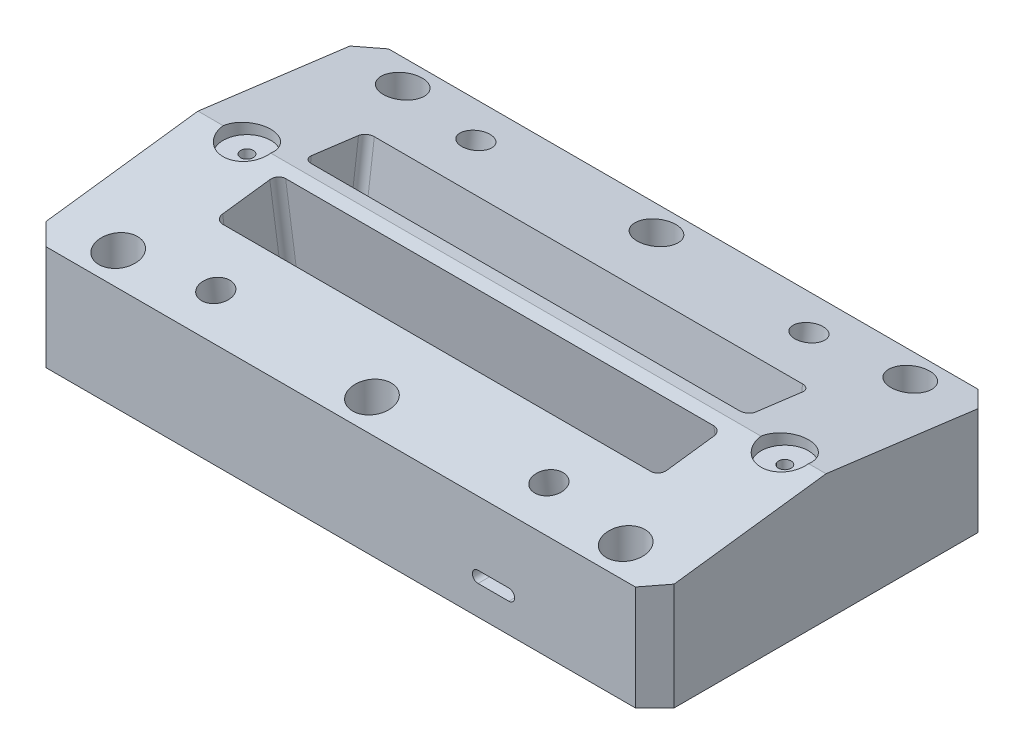
SolidWorks part; units mm, degrees
material "Custom Plastic"
ref_plane "Front Plane" through (0, 0, 0) normal (0, 0, 1) x (1, 0, 0)
ref_plane "Top Plane" through (0, 0, 0) normal (0, 1, 0) x (1, 0, 0)
ref_plane "Right Plane" through (0, 0, 0) normal (1, 0, 0) x (0, 0, -1)
sketch "Sketch1" plane through (0, 0, 0) normal (0, 1, 0) x (1, 0, 0)
  line L1 (0, 0) -> (198, 0)
  line L2 (0, 0) -> (0, 108)
  line L3 (0, 108) -> (198, 108)
  line L4 (198, 0) -> (198, 108)
  dimension "D1" = 198
  dimension "D2" = 108
extrude "Boss-Extrude1" add sketch "Sketch1" along normal blind 40
ref_plane "Left" through (198, 0, 0) normal (1, 0, 0) x (0, 0, -1)
ref_plane "Bot" through (0, 40, 0) normal (0, 1, 0) x (1, 0, 0)
ref_plane "der loco" through (0, 0, -52) normal (0, 0, -1) x (-1, 0, 0)
sketch "Sketch4" plane through (0, 0, 0) normal (0, 1, 0) x (1, 0, 0)
  line L0 (0, 108) -> (0, 0) construction
  line L1 (8.5, 31.5) -> (189.5, 31.5)
  line L2 (8.5, 31.5) -> (8.5, 76.5)
  line L3 (8.5, 76.5) -> (189.5, 76.5)
  line L4 (189.5, 31.5) -> (189.5, 76.5)
  line L5 (0, 0) -> (198, 0) construction
  dimension "D1" = 181
  dimension "D2" = 8.5
  dimension "D3" = 45
  dimension "D4" = 31.5
extrude "Cut-Extrude2" cut sketch "Sketch4" along normal blind 10 contours L2 L1 L4 L3
ref_plane "Plane32" through (0, 10, 0) normal (0, -1, 0) x (-1, 0, 0)
sketch "Sketch5" plane through (198, 0, 0) normal (1, 0, 0) x (0, 0, -1)
  line L0 (54, 40) -> (108, 33.0345)
  line L1 (0, 40) -> (108, 40) construction
  line L2 (108, 33.0345) -> (108, 40)
  line L3 (108, 40) -> (54, 40)
  line L4 (108, 40) -> (108, 0) construction
  dimension "D1" = 7.35
  dimension "D2" = 54
extrude "Cut-Extrude3" cut sketch "Sketch5" against normal up to vertex (198 mm away) up to point (0, 40, 0)
ref_plane "Plane24" through (0, 10, 0) normal (0, -1, 0) x (-1, 0, 0)
sketch "Sketch53" plane through (0, 10, 0) normal (0, -1, 0) x (-1, 0, 0)
  line L0 (-8.5, 51.5) -> (-8.5, 31.5)
  line L1 (-8.5, 76.5) -> (-8.5, 31.5) construction
  line L2 (-8.5, 31.5) -> (-39.5, 31.5)
  line L3 (-8.5, 31.5) -> (-189.5, 31.5) construction
  line L4 (-39.5, 31.5) -> (-8.5, 51.5)
  line L5 (-8.5, 54) -> (-189.5, 54) construction
  line L6 (-189.5, 31.5) -> (-189.5, 76.5) construction
  line L7 (-8.5, 56.5) -> (-8.5, 76.5)
  line L8 (-8.5, 76.5) -> (-39.5, 76.5)
  line L9 (-39.5, 76.5) -> (-8.5, 56.5)
  line L10 (-99, 76.5) -> (-99, 31.5) construction
  line L11 (-8.5, 76.5) -> (-189.5, 76.5) construction
  line L12 (-8.5, 31.5) -> (-189.5, 31.5) construction
  line L13 (-158.5, 76.5) -> (-189.5, 56.5)
  line L14 (-189.5, 76.5) -> (-158.5, 76.5)
  line L15 (-189.5, 56.5) -> (-189.5, 76.5)
  line L16 (-158.5, 31.5) -> (-189.5, 51.5)
  line L17 (-189.5, 31.5) -> (-158.5, 31.5)
  line L18 (-189.5, 51.5) -> (-189.5, 31.5)
  dimension "D1" = 31
  dimension "D2" = 20
extrude "Boss-Extrude11" add sketch "Sketch53" along normal up to surface (10 mm away) up to face at (99, 0, -54)
ref_plane "izq loco" through (0, 0, -57) normal (0, 0, -1) x (-1, 0, 0)
sketch "Sketch18" plane through (198, 0, 0) normal (1, 0, 0) x (0, 0, -1)
  line L0 (0, 33.0345) -> (0, 40)
  line L1 (0, 40) -> (0, 0) construction
  line L2 (0, 40) -> (54, 40)
  line L3 (54, 40) -> (0, 33.0345)
  line L4 (0, 40) -> (54, 40) construction
  dimension "D1" = 54
  dimension "D2" = 7.35
extrude "Cut-Extrude12" cut sketch "Sketch18" against normal up to surface (198 mm away) up to face at (0, 22.6069, -54)
sketch "Sketch60" plane through (0, 0, 0) normal (0, 1, 0) x (1, 0, 0)
  point P0 (8.5, 31.5)
  point P1 (39.5, 31.5)
  point P2 (8.5, 76.5)
  point P6 (39.5, 76.5)
  dimension "D1" = 20
  dimension "D2" = 31
  dimension "D3" = 20
  dimension "D4" = 31
ref_axis "Axis6" through (8.5, 0, -31.5) along (1, 0, 0)
sketch "Sketch69" plane through (0, 10, 0) normal (0, -1, 0) x (-1, 0, 0)
  point P0 (-39.5, 56.5)
  point P1 (-8.5, 51.5)
  point P2 (-38.5, 51.5)
  point P3 (-8.5, 56.5)
  dimension "D1" = 31
  dimension "D2" = 20
  dimension "D3" = 20
  dimension "D4" = 30
sketch "der loco axis" plane through (0, 0, -52) normal (0, 0, -1) x (-1, 0, 0)
  point P0 (-8.5, 8.5)
  point P1 (-38.5, 8.5)
  dimension "D1" = 1.5
sketch "izq loco axis" plane through (0, 0, -57) normal (0, 0, -1) x (-1, 0, 0)
  line L0 (-39.5, 0) -> (-39.5, 10) construction
  line L1 (-8.5, 0) -> (-8.5, 10) construction
  point P0 (-8.5, 8.4959)
  point P1 (-39.5, 8.4959)
  dimension "D1" = 1.5041
ref_plane "Plane3" through (0, 46.1968, -5.9589) normal (0, 0.9918, -0.1279) x (1, 0, 0)
ref_axis "Axis8" through (39.5, 0, -76.5) along (-1, 0, 0)
ref_axis "Axis9" through (8.5, 8.4959, -57) along (1, 0, 0)
ref_axis "Axis10" through (38.5, 8.5, -52) along (-1, 0, 0)
ref_plane "Izq bueno" through (0, 28.0127, -12.2048) normal (0, 0.9168, -0.3994) x (1, 0, 0)
sketch "Izq" plane through (0, 28.0127, -12.2048) normal (0, 0.9168, -0.3994) x (1, 0, 0)
  line L0 (8.5, 48.8622) -> (29.5, 70.1326)
  line L1 (29.5, 70.1326) -> (8.5, 70.1326)
  line L2 (8.5, 70.1326) -> (8.5, 48.8622)
  dimension "D1" = 21
extrude "Cut-Extrude28" cut sketch "Izq" against normal blind 14.5
ref_plane "Der bueno" through (0, -11.1449, -4.6211) normal (0, 0.9237, 0.383) x (1, 0, 0)
sketch "Der" plane through (0, -11.1449, -4.6211) normal (0, 0.9237, 0.383) x (1, 0, 0)
  line L0 (8.5, 51.2902) -> (29.5, 29.0979)
  line L1 (29.5, 29.0979) -> (8.5, 29.0979)
  line L2 (8.5, 29.0979) -> (8.5, 51.2902)
  dimension "D1" = 21
extrude "Cut-Extrude29" cut sketch "Der" against normal blind 14.5
sketch "Sketch97" plane through (0, 0, 0) normal (0, 1, 0) x (1, 0, 0)
  line L0 (8.5, 57.5) -> (29.5, 76.5)
  line L1 (29.5, 76.5) -> (158.5, 76.5)
  line L3 (158.5, 31.5) -> (29.5, 31.5)
  line L4 (29.5, 31.5) -> (8.5, 51.5)
  line L5 (8.5, 51.5) -> (8.5, 57.5)
  line L7 (158.5, 76.5) -> (189.5, 56.5)
  line L8 (189.5, 56.5) -> (189.5, 51.5)
  line L9 (189.5, 51.5) -> (158.5, 31.5)
  line L10 (39.5, 76.5) -> (158.5, 76.5) construction
  dimension "D1" = 6
extrude "Cut-Extrude40" cut sketch "Sketch97" along normal up to surface (10 mm away) up to face at (99, 10, -54)
ref_axis "Axis11" through (99, 0, -108) along (0, 0, 1)
ref_plane "Plane33" through (99, 0, 0) normal (1, 0, 0) x (0, 0, -1)
mirror "Mirror2" about plane through (99, 0, 0) normal (1, 0, 0) of "Cut-Extrude29", "Cut-Extrude40", "Cut-Extrude28"
sketch "Sketch6" plane through (0, 46.1968, -5.9589) normal (0, 0.9918, -0.1279) x (1, 0, 0)
  line L0 (0, 48.4391) -> (198, 48.4391) construction
  line L1 (28.9, 75.8391) -> (169.5, 75.8391)
  line L2 (25.9, 72.8391) -> (25.9, 52.2391)
  line L3 (28.9, 49.2391) -> (169.5, 49.2391)
  line L4 (172.5, 72.8391) -> (172.5, 52.2391)
  line L7 (28.6, 51.9391) -> (169.8, 51.9391)
  line L8 (28.6, 51.9391) -> (28.6, 73.1391)
  line L9 (28.6, 73.1391) -> (169.8, 73.1391)
  line L10 (169.8, 51.9391) -> (169.8, 73.1391)
  line L13 (198, 48.4391) -> (198, 102.8865) construction
  arc A0 (169.5, 75.8391) -> (172.5, 72.8391) centre (169.5, 72.8391) cw
  arc A1 (169.5, 49.2391) -> (172.5, 52.2391) centre (169.5, 52.2391) ccw
  arc A2 (25.9, 52.2391) -> (28.9, 49.2391) centre (28.9, 52.2391) ccw
  arc A3 (28.9, 75.8391) -> (25.9, 72.8391) centre (28.9, 72.8391) ccw
  dimension "D1" = 3
  dimension "D2" = 146.6
  dimension "D3" = 20.6
  dimension "D4" = 25.5
  dimension "D5" = 3.5
  dimension "D6" = 2.7
  dimension "D7" = 2.7
  dimension "D8" = 2.7
  dimension "D9" = 2.7
sketch "Sketch9" plane through (0, 40, 0) normal (0, 1, 0) x (1, 0, 0)
  line L1 (0, 54) -> (198, 54) construction
  circle A0 centre (15.45, 54) radius 8
  dimension "D1" = 16
  dimension "D2" = 15.45
sketch "Sketch12" plane through (0, 40, 0) normal (0, 1, 0) x (1, 0, 0)
  line L1 (0, 108) -> (198, 108) construction
  line L4 (0, 0) -> (198, 0) construction
  circle A0 centre (19.7, 98.85) radius 3.15
  circle A1 centre (99.7, 9.15) radius 3.15
  circle A2 centre (179.7, 9.15) radius 3.15
  circle A3 centre (19.7, 9.15) radius 3.15
  circle A4 centre (99.7, 98.85) radius 3.15
  circle A5 centre (179.7, 98.85) radius 3.15
  dimension "D1" = 9.15
  dimension "D2" = 6.3
  dimension "D3" = 9.15
  dimension "D4" = 19.7
  dimension "D7" = 80
  dimension "D9" = 80
extrude "Cut-Extrude9" cut sketch "Sketch12" against normal through all
sketch "Sketch13" plane through (0, 46.1968, -5.9589) normal (0, 0.9918, -0.1279) x (1, 0, 0)
  line L1 (0, 102.8865) -> (198, 102.8865) construction
  line L2 (198, 48.4391) -> (198, 102.8865) construction
  line L3 (0, 48.4391) -> (0, 102.8865) construction
  circle A0 centre (46.5, 89.8865) radius 4.5
  circle A1 centre (151.5, 89.8865) radius 4.5
  dimension "D1" = 9
  dimension "D4" = 9
  dimension "D2" = 46.5
  dimension "D3" = 13
  dimension "D5" = 46.5
extrude "Cut-Extrude10" cut sketch "Sketch13" against normal blind 16.5
sketch "Sketch14" plane through (0, 32.1182, 7.1038) normal (0, 0.9918, 0.1279) x (1, 0, 0)
  line L3 (198, 7.1626) -> (198, 61.61) construction
  line L4 (0, 61.61) -> (198, 61.61) construction
  circle A0 centre (46.5, 20.3915) radius 4.5
  circle A1 centre (151.5, 20.3915) radius 4.5
  dimension "D1" = 9
  dimension "D2" = 9
  dimension "D3" = 46.5
  dimension "D4" = 41.2185
  dimension "D5" = 46.5
extrude "Cut-Extrude11" cut sketch "Sketch14" against normal blind 16.5
ref_plane "Plane9" through (0, 32.4939, 4.1914) normal (0, 0.9918, 0.1279) x (1, 0, 0)
sketch "Sketch23" plane through (0, 32.4939, 4.1914) normal (0, 0.9918, 0.1279) x (1, 0, 0)
  line L0 (0, 58.6735) -> (198, 58.6735) construction
  line L1 (28.9, 57.8735) -> (169.5, 57.8735)
  line L2 (25.9, 54.8735) -> (25.9, 34.2735)
  line L3 (28.9, 31.2735) -> (169.5, 31.2735)
  line L4 (172.5, 54.8735) -> (172.5, 34.2735)
  line L7 (28.6, 55.1735) -> (169.8, 55.1735)
  line L8 (28.6, 55.1735) -> (28.6, 33.9735)
  line L9 (28.6, 33.9735) -> (169.8, 33.9735)
  line L10 (169.8, 55.1735) -> (169.8, 33.9735)
  line L12 (198, 4.2261) -> (198, 58.6735) construction
  arc A0 (169.5, 57.8735) -> (172.5, 54.8735) centre (169.5, 54.8735) cw
  arc A1 (169.5, 31.2735) -> (172.5, 34.2735) centre (169.5, 34.2735) ccw
  arc A2 (25.9, 34.2735) -> (28.9, 31.2735) centre (28.9, 34.2735) ccw
  arc A3 (28.9, 57.8735) -> (25.9, 54.8735) centre (28.9, 54.8735) ccw
  point P10 (172.5, 57.8735)
  point P15 (25.9, 31.2735)
  point P18 (25.9, 57.8735)
  dimension "D5" = 3
  dimension "D1" = 146.6
  dimension "D2" = 20.6
  dimension "D3" = 3.5
  dimension "D4" = 25.5
  dimension "D6" = 2.7
  dimension "D7" = 2.7
  dimension "D8" = 2.7
  dimension "D9" = 2.7
sketch "Sketch41" plane through (0, 0, 0) normal (0, 1, 0) x (1, 0, 0)
  line L0 (198, 0) -> (198, 108) construction
  line L1 (198, 108) -> (0, 108) construction
  line L2 (0, 0) -> (198, 0) construction
  circle A0 centre (139.5, 9) radius 2.9
  circle A1 centre (139.5, 99) radius 2.9
  dimension "D1" = 5.8
  dimension "D4" = 5.8
  dimension "D2" = 58.5
  dimension "D3" = 58.5
  dimension "D5" = 9
  dimension "D6" = 9
extrude "Cut-Extrude21" cut sketch "Sketch41" along normal blind 7
sketch "Sketch42" plane through (0, 0, 0) normal (0, 0, 1) x (1, 0, 0)
  line L0 (198, 33.0345) -> (198, 0) construction
  line L5 (0, 0) -> (198, 0) construction
  line L6 (142.3, 12.8) -> (152, 12.8)
  line L7 (142.3, 9.2) -> (152, 9.2)
  arc A0 (142.3, 12.8) -> (142.3, 9.2) centre (142.3, 11) ccw
  arc A2 (152, 12.8) -> (152, 9.2) centre (152, 11) cw
  dimension "D2" = 1.8
  dimension "D3" = 1.8
  dimension "D1" = 9.7
  dimension "D5" = 46
  dimension "D6" = 11
extrude "Cut-Extrude22" cut sketch "Sketch42" against normal blind 10
ref_plane "Plane19" through (0, 0, -108) normal (0, 0, -1) x (-1, 0, 0)
sketch "Sketch43" plane through (0, 0, -108) normal (0, 0, -1) x (-1, 0, 0)
  line L0 (-55.7, 11) -> (-46, 11) construction
  line L1 (-55.7, 12.8) -> (-46, 12.8)
  line L2 (-55.7, 9.2) -> (-46, 9.2)
  line L3 (-198, 0) -> (0, 0) construction
  line L4 (0, 33.0345) -> (0, 0) construction
  arc A0 (-55.7, 12.8) -> (-55.7, 9.2) centre (-55.7, 11) ccw
  arc A1 (-46, 9.2) -> (-46, 12.8) centre (-46, 11) ccw
  point P2 (-50.85, 11)
  dimension "D2" = 1.8
  dimension "D1" = 9.7
  dimension "D3" = 11
  dimension "D4" = 46
extrude "Cut-Extrude23" cut sketch "Sketch43" against normal blind 10
sketch "Sketch84" plane through (0, 46.1968, -5.9589) normal (0, 0.9918, -0.1279) x (1, 0, 0)
  line L0 (0, 48.4391) -> (198, 48.4391) construction
  line L1 (31.7, 52.5391) -> (166.7, 52.5391)
  line L2 (29.2, 55.0391) -> (29.2, 70.0391)
  line L3 (31.7, 72.5391) -> (166.7, 72.5391)
  line L4 (169.2, 55.0391) -> (169.2, 70.0391)
  line L7 (0, 48.4391) -> (0, 102.8865) construction
  arc A0 (166.7, 52.5391) -> (169.2, 55.0391) centre (166.7, 55.0391) ccw
  arc A1 (166.7, 72.5391) -> (169.2, 70.0391) centre (166.7, 70.0391) cw
  arc A2 (29.2, 70.0391) -> (31.7, 72.5391) centre (31.7, 70.0391) cw
  arc A3 (31.7, 52.5391) -> (29.2, 55.0391) centre (31.7, 55.0391) cw
  point P10 (169.2, 52.5391)
  point P13 (169.2, 72.5391)
  point P16 (29.2, 72.5391)
  point P19 (169.2, 62.5391)
  dimension "D5" = 2.5
  dimension "D1" = 140
  dimension "D2" = 20
  dimension "D3" = 4.1
  dimension "D4" = 29.2
extrude "Cut-Extrude35" cut sketch "Sketch84" against normal blind 55.4
sketch "Sketch83" plane through (0, 32.4939, 4.1914) normal (0, 0.9918, 0.1279) x (1, 0, 0)
  line L1 (31.7, 54.5735) -> (166.7, 54.5735)
  line L2 (29.2, 52.0735) -> (29.2, 37.0735)
  line L3 (31.7, 34.5735) -> (166.7, 34.5735)
  line L4 (169.2, 52.0735) -> (169.2, 37.0735)
  line L7 (0, 58.6735) -> (198, 58.6735) construction
  line L8 (0, 58.6735) -> (0, 4.2261) construction
  arc A0 (166.7, 34.5735) -> (169.2, 37.0735) centre (166.7, 37.0735) ccw
  arc A1 (166.7, 54.5735) -> (169.2, 52.0735) centre (166.7, 52.0735) cw
  arc A2 (29.2, 37.0735) -> (31.7, 34.5735) centre (31.7, 37.0735) ccw
  arc A3 (31.7, 54.5735) -> (29.2, 52.0735) centre (31.7, 52.0735) ccw
  point P12 (169.2, 54.5735)
  point P15 (29.2, 34.5735)
  point P18 (29.2, 54.5735)
  point P19 (169.2, 44.5735)
  dimension "D5" = 2.5
  dimension "D1" = 140
  dimension "D2" = 20
  dimension "D3" = 29.2
  dimension "D4" = 4.1
extrude "Cut-Extrude34" cut sketch "Sketch83" against normal blind 55.4
sketch "Sketch85" plane through (0, 40, 0) normal (0, 1, 0) x (1, 0, 0)
  line L0 (0, 101.9) -> (6.1, 108)
  line L3 (6.1, 108) -> (0, 108)
  line L4 (0, 108) -> (0, 101.9)
  line L5 (0, 0) -> (6.1, 0)
  line L7 (6.1, 0) -> (0, 6.1)
  line L9 (0, 6.1) -> (0, 0)
  line L10 (198, 6.1) -> (191.9, 0)
  line L11 (198, 0) -> (198, 54) construction
  line L12 (0, 0) -> (198, 0) construction
  line L13 (191.9, 0) -> (198, 0)
  line L14 (198, 0) -> (198, 6.1)
  line L15 (198, 108) -> (191.9, 108)
  line L16 (0, 108) -> (198, 108) construction
  line L17 (191.9, 108) -> (198, 101.9)
  line L18 (198, 54) -> (198, 108) construction
  line L19 (198, 101.9) -> (198, 108)
  line L20 (0, 54) -> (0, 108) construction
  line L21 (0, 108) -> (198, 108) construction
  line L22 (0, 0) -> (198, 0) construction
  line L23 (0, 54) -> (0, 0) construction
  dimension "D1" = 6.1
  dimension "D2" = 6.1
  dimension "D3" = 6.1
  dimension "D4" = 6.1
  dimension "D5" = 6.1
  dimension "D6" = 6.1
  dimension "D7" = 6.1
extrude "Cut-Extrude36" cut sketch "Sketch85" against normal blind 55.4
sketch "Sketch90" plane through (0, 40, 0) normal (0, 1, 0) x (1, 0, 0)
  circle A0 centre (19.7, 9.15) radius 6.1
  circle A1 centre (99.7, 9.15) radius 6.1
  circle A2 centre (179.7, 9.15) radius 6.1
  circle A3 centre (99.7, 98.85) radius 6.1
  circle A4 centre (179.7, 98.85) radius 6.1
  circle A5 centre (19.7, 98.85) radius 6.1
  circle A6 centre (179.7, 98.85) radius 3.15 construction
  circle A7 centre (99.7, 98.85) radius 3.15 construction
  dimension "D1" = 12.2
  dimension "D2" = 3
  dimension "D3" = 2
extrude "Cut-Extrude38" cut sketch "Sketch90" against normal blind 17
sketch "Sketch96" plane through (0, 0, 0) normal (0, 1, 0) x (1, 0, 0)
  line L0 (0, 54) -> (198, 54) construction
  line L1 (198, 6.1) -> (198, 101.9) construction
  circle A0 centre (15.45, 54) radius 2
  circle A1 centre (185, 54) radius 2
  dimension "D1" = 4
  dimension "D2" = 4
  dimension "D3" = 13
extrude "Cut-Extrude39" cut sketch "Sketch96" along normal through all
sketch "Sketch98" plane through (0, 40, 0) normal (0, 1, 0) x (1, 0, 0)
  circle A0 centre (185, 54) radius 7.5
  circle A1 centre (15.45, 54) radius 7.5
  dimension "D1" = 15
  dimension "D2" = 15
extrude "Cut-Extrude41" cut sketch "Sketch98" against normal blind 4
sketch "Sketch99" plane through (198, 0, 0) normal (1, 0, 0) x (0, 0, -1)
  line L0 (57.4712, 39.5522) -> (78.497, 36.8401) construction
  line L1 (54, -71.51) -> (67.9841, 38.1962) construction
  line L2 (54, -71.51) -> (110.6804, -78.8212) construction
  line L3 (54, 40) -> (101.9, 33.8214) construction
  line L4 (54, -71.51) -> (-2.6804, -78.8212) construction
  line L5 (6.1, 33.8214) -> (54, 40) construction
  line L6 (54.1669, -71.51) -> (40.0159, 38.1962) construction
  line L7 (-3.15, -71.51) -> (111.15, -71.51) construction
  line L8 (54, -71.51) -> (40.0159, 38.1962) construction
  line L9 (32.5775, 37.2367) -> (47.4542, 39.1557) construction
  line L10 (53.8331, -71.51) -> (67.9841, 38.1962) construction
  circle A1 centre (54, -71.51) radius 57.15
  point P0 (-2.9675, -76.0735)
  point P1 (54, -76.9108)
  point P19 (40.0159, 38.1962)
  point P21 (0, 0)
  point P22 (53.9985, -76.1275)
  dimension "D1" = 71.51
  dimension "D5" = 114.3
  dimension "D3" = 90.086
  dimension "D4" = 90.086
